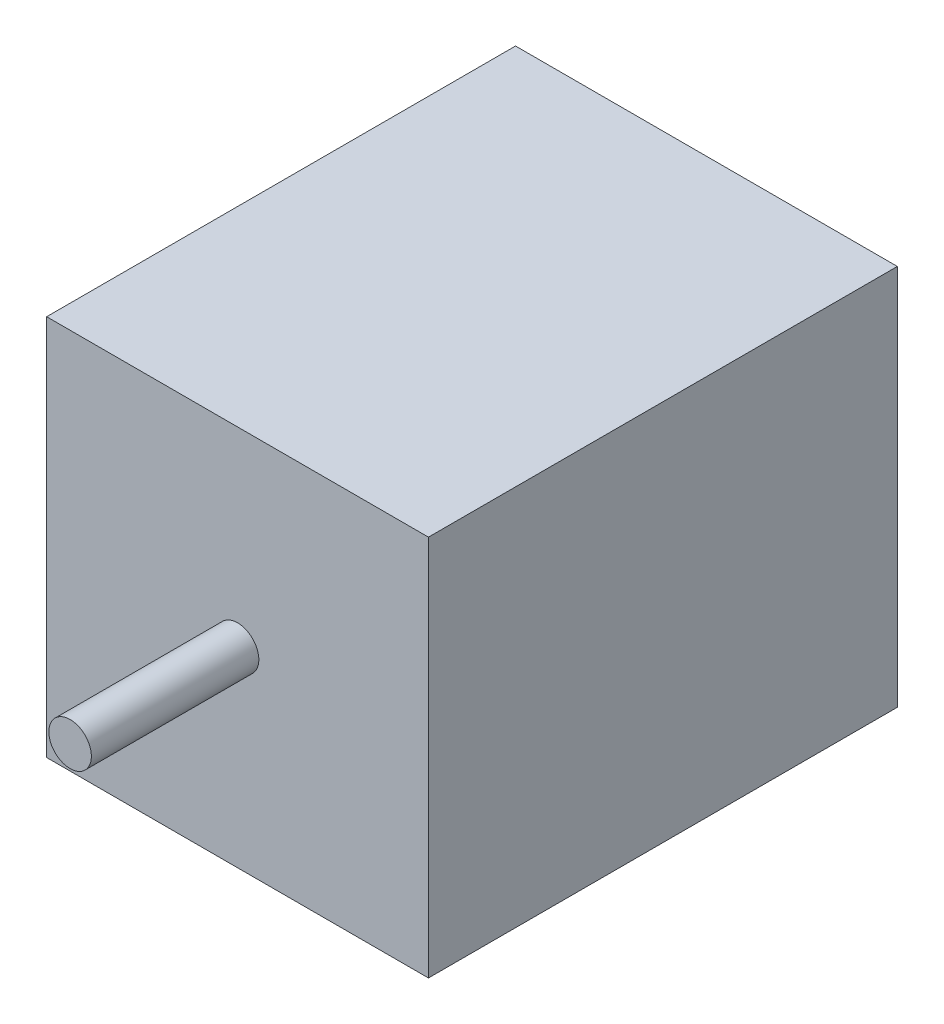
SolidWorks part; units mm, degrees
ref_plane "Front Plane" through (0, 0, 0) normal (0, 0, 1) x (1, 0, 0)
ref_plane "Top Plane" through (0, 0, 0) normal (0, 1, 0) x (1, 0, 0)
ref_plane "Right Plane" through (0, 0, 0) normal (1, 0, 0) x (0, 0, -1)
sketch "Sketch1" plane through (0, 0, 0) normal (0, 0, 1) x (1, 0, 0)
  line L1 (-28.5, -28.5) -> (28.5, -28.5)
  line L2 (-28.5, -28.5) -> (-28.5, 28.5)
  line L3 (-28.5, 28.5) -> (28.5, 28.5)
  line L4 (28.5, -28.5) -> (28.5, 28.5)
  line L5 (-28.5, -28.5) -> (28.5, 28.5) construction
  line L6 (-28.5, 28.5) -> (28.5, -28.5) construction
  point P0 (0, 0)
  dimension "D1" = 57
  dimension "D2" = 57
extrude "Boss-Extrude1" add sketch "Sketch1" along normal mid plane 70
sketch "Sketch2" plane through (0, 0, 35) normal (0, 0, 1) x (1, 0, 0)
  circle A0 centre (0, 0) radius 3.175
  dimension "D1" = 6.35
extrude "Boss-Extrude2" add sketch "Sketch2" along normal blind 25
